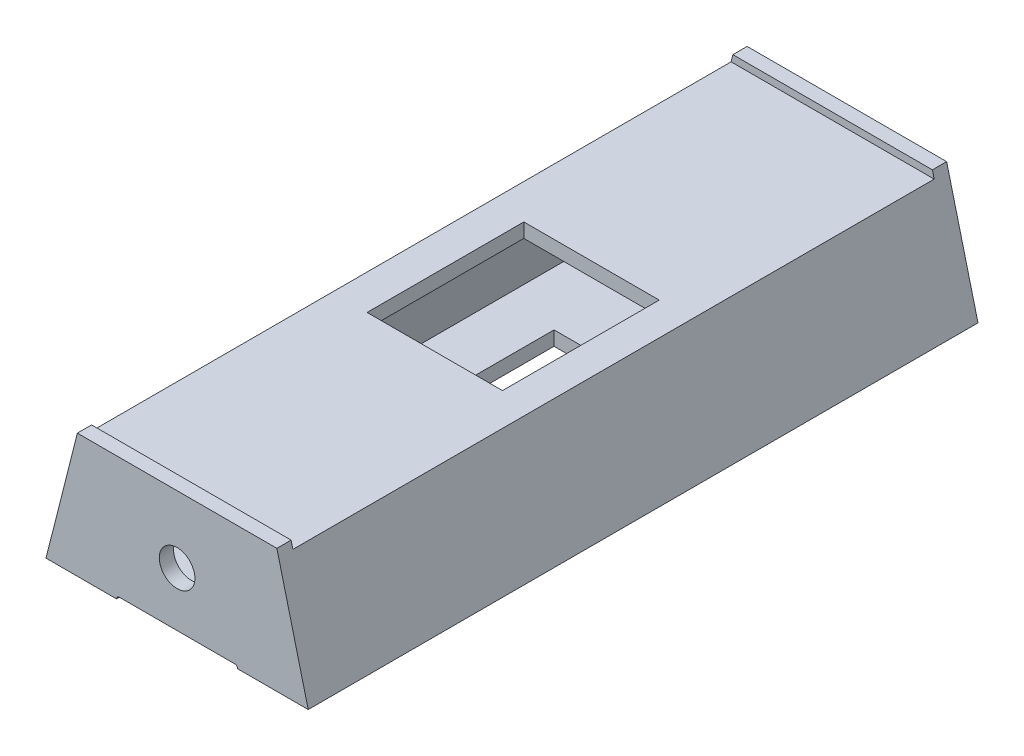
SolidWorks part; units mm, degrees
ref_plane "Płaszczyzna przednia" through (0, 0, 0) normal (0, 0, 1) x (1, 0, 0)
ref_plane "Płaszczyzna górna" through (0, 0, 0) normal (0, 1, 0) x (1, 0, 0)
ref_plane "Płaszczyzna prawa" through (0, 0, 0) normal (1, 0, 0) x (0, 0, -1)
sketch "Szkic1" plane through (0, 0, 0) normal (0, 0, 1) x (1, 0, 0)
  line L0 (70, 47) -> (-70, 47)
  line L1 (-70, 47) -> (-92, -40)
  line L2 (-92, -40) -> (92, -40)
  line L3 (0, -55) -> (0, 55) construction
  line L4 (70, 47) -> (92, -40)
  point P7 (0, -40)
  point P8 (0, 47)
  dimension "D1" = 184
  dimension "D2" = 140
  dimension "D3" = 87
  dimension "D4" = 40
extrude "Dodanie-wyciągnięcie1" add sketch "Szkic1" along normal blind 10
sketch "Szkic2" plane through (0, 0, 0) normal (0, 0, -1) x (-1, 0, 0)
  circle A0 centre (0, 0) radius 14
extrude "Wytnij-wyciągnięcie1" cut sketch "Szkic2" against normal up to next
sketch "Szkic3" plane through (0, 0, 10) normal (0, 0, 1) x (1, 0, 0)
  line L0 (-71.2644, 42) -> (71.2644, 42)
  line L1 (70, 47) -> (-70, 47) construction
  line L4 (-70, 47) -> (-92, -40)
  line L5 (-92, -40) -> (92, -40)
  line L6 (92, -40) -> (70, 47)
  line L7 (70, 47) -> (-70, 47)
  line L8 (-71.2644, 42) -> (-92, -40)
  line L9 (-92, -40) -> (92, -40)
  line L10 (92, -40) -> (71.2644, 42)
  line L14 (-63.4783, 32) -> (63.4783, 32)
  line L15 (63.4783, 32) -> (78.6507, -28)
  line L16 (78.6507, -28) -> (-78.6507, -28)
  line L17 (-78.6507, -28) -> (-63.4783, 32)
  dimension "D2" = 5
  dimension "D4" = 10
  dimension "D3" = 10
  dimension "D5" = 10
  dimension "D6" = 12
  dimension "D1" = 0
extrude "Dodanie-wyciągnięcie2" add sketch "Szkic3" along normal blind 450
sketch "Szkic4" plane through (0, 0, 460) normal (0, 0, 1) x (1, 0, 0)
  line L4 (-70, 47) -> (-92, -40)
  line L5 (70, 47) -> (-70, 47)
  line L6 (92, -40) -> (70, 47)
  line L7 (-92, -40) -> (92, -40)
  line L8 (-70, 47) -> (-92, -40)
  line L9 (70, 47) -> (-70, 47)
  line L10 (92, -40) -> (70, 47)
  line L11 (-92, -40) -> (92, -40)
  dimension "D1" = 0
extrude "Dodanie-wyciągnięcie3" add sketch "Szkic4" along normal blind 10
sketch "Szkic5" plane through (0, 0, 470) normal (0, 0, 1) x (1, 0, 0)
  circle A0 centre (0, 0) radius 12.5
extrude "Wytnij-wyciągnięcie2" cut sketch "Szkic5" against normal up to next
sketch "Szkic7" plane through (0, -40, 0) normal (0, -1, 0) x (1, 0, 0)
  line L1 (-42.5, 0) -> (42.5, 0)
  line L2 (-42.5, 0) -> (-42.5, 470)
  line L3 (-42.5, 470) -> (42.5, 470)
  line L4 (42.5, 0) -> (42.5, 470)
  line L5 (-42.5, 0) -> (42.5, 470) construction
  line L6 (-42.5, 470) -> (42.5, 0) construction
  line L7 (-92, 0) -> (92, 0) construction
  line L8 (-92, 470) -> (92, 470) construction
  point P0 (0, 235)
  point P10 (0, 0)
  point P16 (0, 0)
  point P17 (0, 0)
  dimension "D1" = 85
extrude "Wytnij-wyciągnięcie3" cut sketch "Szkic7" against normal blind 2
fillet "Zaokrąglenie1" radius 2 2 edges at (42.5, -38, 235) (-42.5, -38, 235)
sketch "Szkic8" plane through (0, -38, 0) normal (0, -1, 0) x (1, 0, 0)
  line L0 (0, -1000) -> (0, 49000) construction
  line L1 (40.5, 0) -> (40.5, 470) construction
  line L2 (-40.5, 165) -> (40.5, 165)
  line L3 (-40.5, 165) -> (-40.5, 305)
  line L4 (-40.5, 305) -> (40.5, 305)
  line L5 (40.5, 165) -> (40.5, 305)
  line L6 (-40.5, 165) -> (40.5, 305) construction
  line L7 (-40.5, 305) -> (40.5, 165) construction
  point P1 (0, 235)
  dimension "D1" = 140
  dimension "D2" = 235
  dimension "D3" = 81
extrude "Wytnij-wyciągnięcie4" cut sketch "Szkic8" against normal up to next
sketch "Szkic9" plane through (0, 42, 0) normal (0, 1, 0) x (1, 0, 0)
  line L0 (70, -470) -> (-70, -470) construction
  line L1 (-46.6941, -290) -> (48.3059, -290)
  line L2 (-46.6941, -290) -> (-46.6941, -180)
  line L3 (-46.6941, -180) -> (48.3059, -180)
  line L4 (48.3059, -290) -> (48.3059, -180)
  line L5 (-46.6941, -290) -> (48.3059, -180) construction
  line L6 (-46.6941, -180) -> (48.3059, -290) construction
  point P0 (0.8059, -235)
  dimension "D1" = 95
  dimension "D2" = 110
  dimension "D3" = 235
extrude "Wytnij-wyciągnięcie5" cut sketch "Szkic9" against normal up to next
